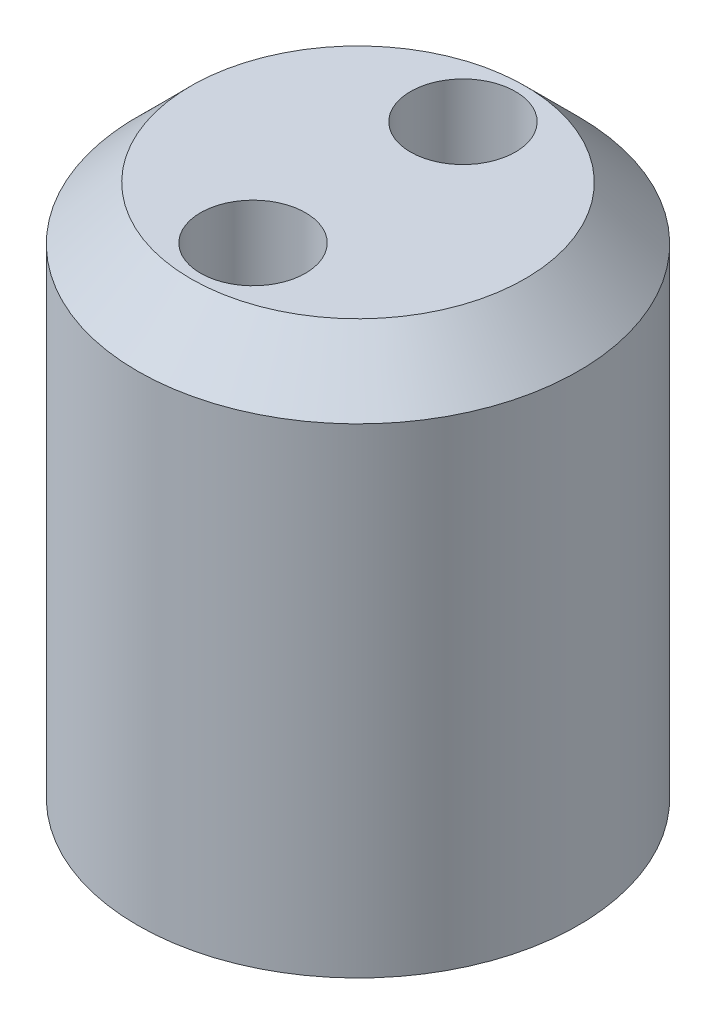
SolidWorks part; units mm, degrees
ref_plane "Front Plane" through (0, 0, 0) normal (0, 0, 1) x (1, 0, 0)
ref_plane "Top Plane" through (0, 0, 0) normal (0, 1, 0) x (1, 0, 0)
ref_plane "Right Plane" through (0, 0, 0) normal (1, 0, 0) x (0, 0, -1)
sketch "Sketch1" plane through (0, 0, 0) normal (0, 1, 0) x (1, 0, 0)
  line L0 (0, -5) -> (0, 5) construction
  circle A0 centre (0, 0) radius 10.5
  circle A2 centre (0, 5) radius 2.5
  circle A3 centre (0, -5) radius 2.5
  dimension "D1" = 21
  dimension "D2" = 5
  dimension "D3" = 10
extrude "Boss-Extrude1" add sketch "Sketch1" along normal blind 25.4
chamfer "Chamfer1" distance 2.54 angle 45 1 edges at (0, 25.4, 10.5)
equation "\"cf_tube_outer_diameter\" = 25mm"
equation "\"cf_tube_inner_diameter\" = 21mm"
equation "\"mid_plate_mid_to_top\" = 100mm"
equation "\"mid_plate_mid_to_bottom\" = 30mm"
equation "\"mid_plate_horizontal_spacing\" = 250mm"
equation "\"cf_plate_thickness\" = 4mm"
equation "\"mid_tube_length\" = 500mm"
equation "\"D1@Sketch1\"=\"cf_tube_inner_diameter\""
